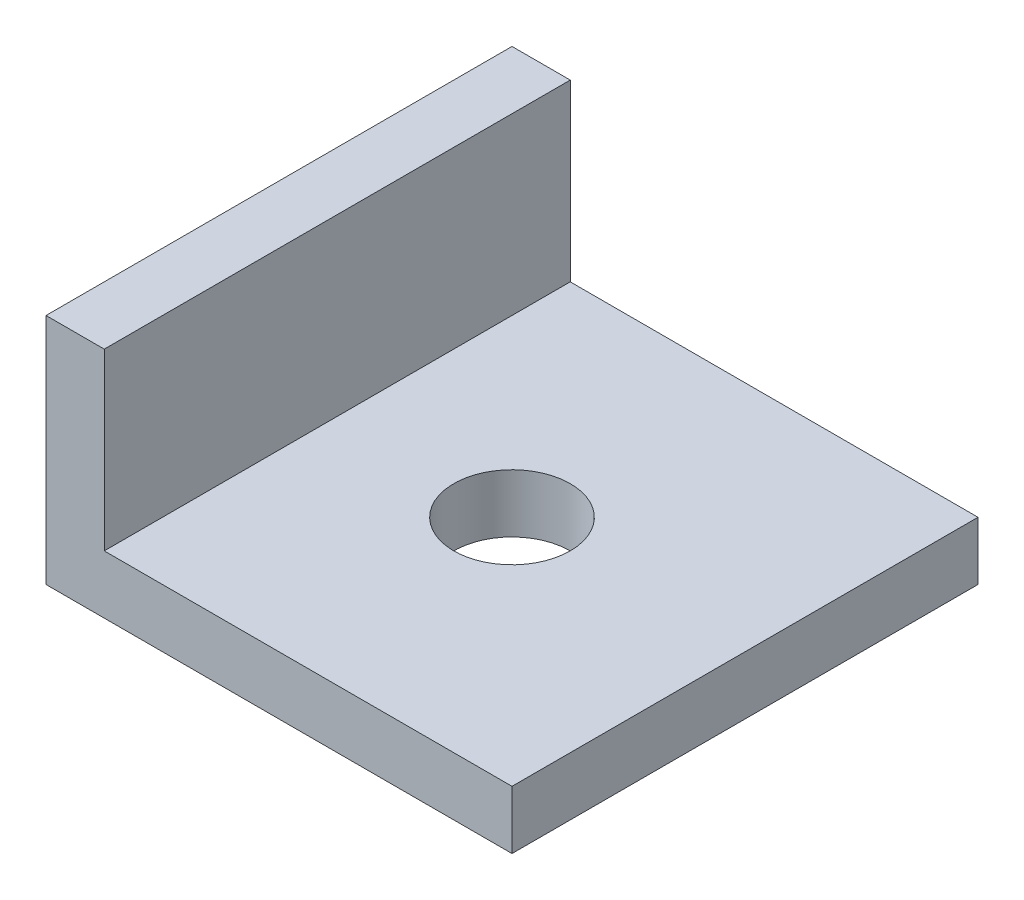
SolidWorks part; units mm, degrees
ref_plane "Front Plane" through (0, 0, 0) normal (0, 0, 1) x (1, 0, 0)
ref_plane "Top Plane" through (0, 0, 0) normal (0, 1, 0) x (1, 0, 0)
ref_plane "Right Plane" through (0, 0, 0) normal (1, 0, 0) x (0, 0, -1)
sketch "Sketch1" plane through (0, 0, 0) normal (0, 0, 1) x (1, 0, 0)
  line L0 (0, 0) -> (0, 50.8)
  line L1 (0, 0) -> (50.8, 0)
  line L2 (50.8, 0) -> (50.8, 6.35)
  line L3 (50.8, 6.35) -> (6.35, 6.35)
  line L4 (6.35, 6.35) -> (6.35, 50.8)
  line L5 (6.35, 50.8) -> (0, 50.8)
  dimension "D1" = 50.8
  dimension "D2" = 6.35
extrude "Boss-Extrude1" add sketch "Sketch1" along normal blind 25.4 and the other way blind 25.4
sketch "Sketch2" plane through (0, 0, 0) normal (-1, 0, 0) x (0, 0, 1)
  line L0 (25.4, 50.8) -> (-25.4, 50.8) construction
  line L1 (-25.4, 50.8) -> (25.4, 50.8)
  line L2 (-25.4, 50.8) -> (-25.4, 25.4)
  line L3 (-25.4, 25.4) -> (25.4, 25.4)
  line L4 (25.4, 50.8) -> (25.4, 25.4)
  line L5 (-25.4, 50.8) -> (25.4, 25.4) construction
  line L6 (-25.4, 25.4) -> (25.4, 50.8) construction
  line L7 (25.4, 50.8) -> (25.4, 0) construction
  line L8 (25.4, 0) -> (-25.4, 0) construction
  point P4 (0, 38.1)
  dimension "D1" = 25.4
extrude "Cut-Extrude1" cut sketch "Sketch2" against normal through all
sketch "Sketch3" plane through (0, 0, 0) normal (0, -1, 0) x (1, 0, 0)
  line L0 (25.4, 25.4) -> (25.4, 0) construction
  line L1 (0, 25.4) -> (50.8, 25.4) construction
  line L2 (25.4, 0) -> (0, 0) construction
  line L3 (0, 25.4) -> (0, -25.4) construction
  circle A0 centre (25.4, 0) radius 6.35
  dimension "D1" = 12.7
extrude "Cut-Extrude2" cut sketch "Sketch3" against normal through all and the other way through all
